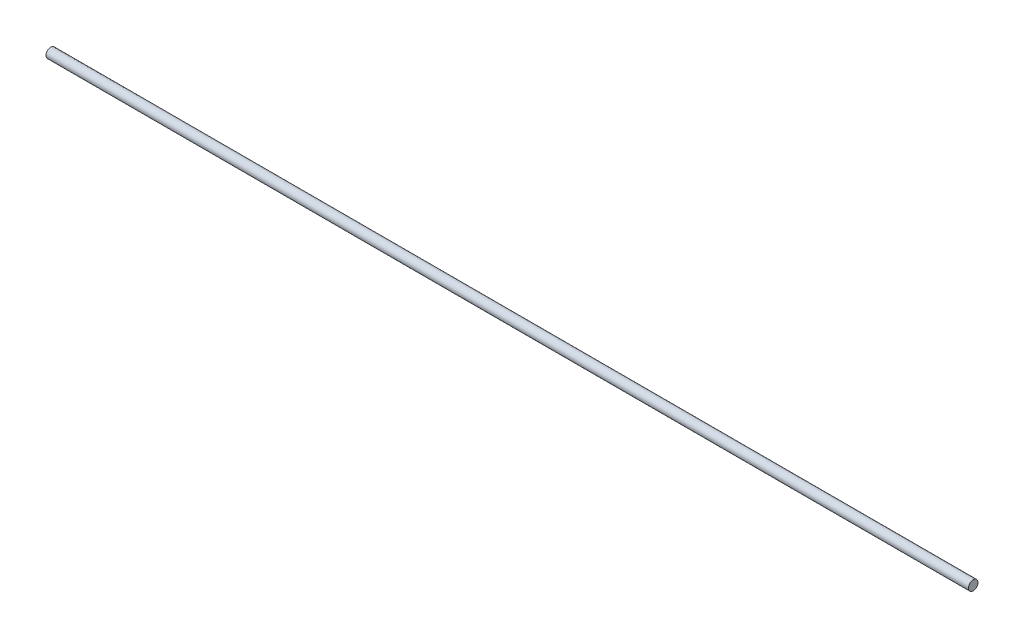
SolidWorks part; units mm, degrees
material "Dowel Wood"
ref_plane "Front Plane" through (0, 0, 0) normal (0, 0, 1) x (1, 0, 0)
ref_plane "Top Plane" through (0, 0, 0) normal (0, 1, 0) x (1, 0, 0)
ref_plane "Right Plane" through (0, 0, 0) normal (1, 0, 0) x (0, 0, -1)
sketch "Sketch1" plane through (0, 0, 0) normal (1, 0, 0) x (0, 0, -1)
  circle A0 centre (0, 0) radius 9.525
extrude "Boss-Extrude1" add sketch "Sketch1" along normal blind 1828.8
